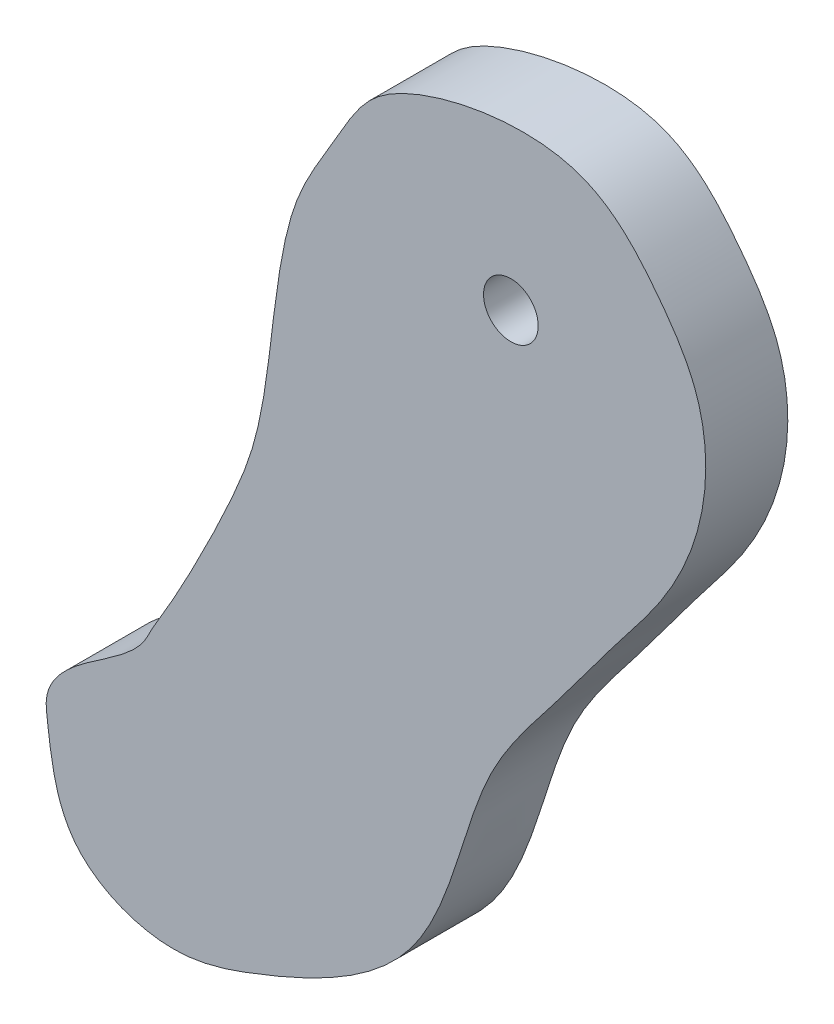
SolidWorks part; units mm, degrees
ref_plane "Спереди" through (0, 0, 0) normal (0, 0, 1) x (1, 0, 0)
ref_plane "Сверху" through (0, 0, 0) normal (0, 1, 0) x (1, 0, 0)
ref_plane "Справа" through (0, 0, 0) normal (1, 0, 0) x (0, 0, -1)
other "Configuration Table"
sketch "Sketch1" plane through (0, 0, 0) normal (0, 0, 1) x (1, 0, 0)
  circle A1 centre (3.0714, 15.9426) radius 1
  spline S0 degree 3 poles (-13.755, -6.5461) (-14.0588, -3.9558) (-10.5195, -1.8472) (-10.1595, -0.7399) (-9.273, 0.4504) (-6.6046, 5.8687) (-5.8643, 8.4353) (-5.2631, 14.9937) (-2.8881, 18.8302) (-1.9561, 21.0714) (5.3929, 22.6269) (8.2701, 19.4445) (10.1888, 16.6288) (10.3461, 13.0124) (8.937, 9.7887) (6.7534, 7.1307) (4.749, 4.3113) (2.0459, 1.0845) (1.136, -2.7938) (-0.883, -7.3396) (-5.1133, -9.3907) (-9.4827, -10.8853) (-13.4151, -9.3478) (-13.755, -6.5461) (-14.0588, -3.9558) (-10.5195, -1.8472) knots -0.091065 -0.04756 -0.004756 0 0.038892 0.095791 0.170637 0.206388 0.248875 0.278359 0.297921 0.348786 0.419462 0.462881 0.494962 0.536061 0.58187 0.614364 0.655354 0.702627 0.75804 0.792049 0.871888 0.908935 0.95244 0.995244 1 1.038892 1.095791 1.170637 only from (-13.9188, -4.9833) to (-13.9188, -4.9833)
  dimension "D1" = 2
extrude "Boss-Extrude1" add sketch "Sketch1" along normal blind 3 contours S0 A1 region at (-1.3011, 5.9988, 0)
ref_plane "Plane2" through (0, 0, 0) normal (0, 0, -1) x (-1, 0, 0)
sketch "Sketch2" plane through (0, 0, 0) normal (0, 0, -1) x (-1, 0, 0)
  circle A0 centre (10.3025, -6.5102) radius 1
  circle A1 centre (-3.0714, 15.9426) radius 1 construction
extrude "Boss-Extrude2" add sketch "Sketch2" along normal blind 3 contours A0
equation "\"R small\"= 2"
equation "\"R big\"= 4"
equation "\"width\"= 0.6"
equation "\"border width\"= 1"
equation "\"D1@Sketch1\"=\"R small\""
